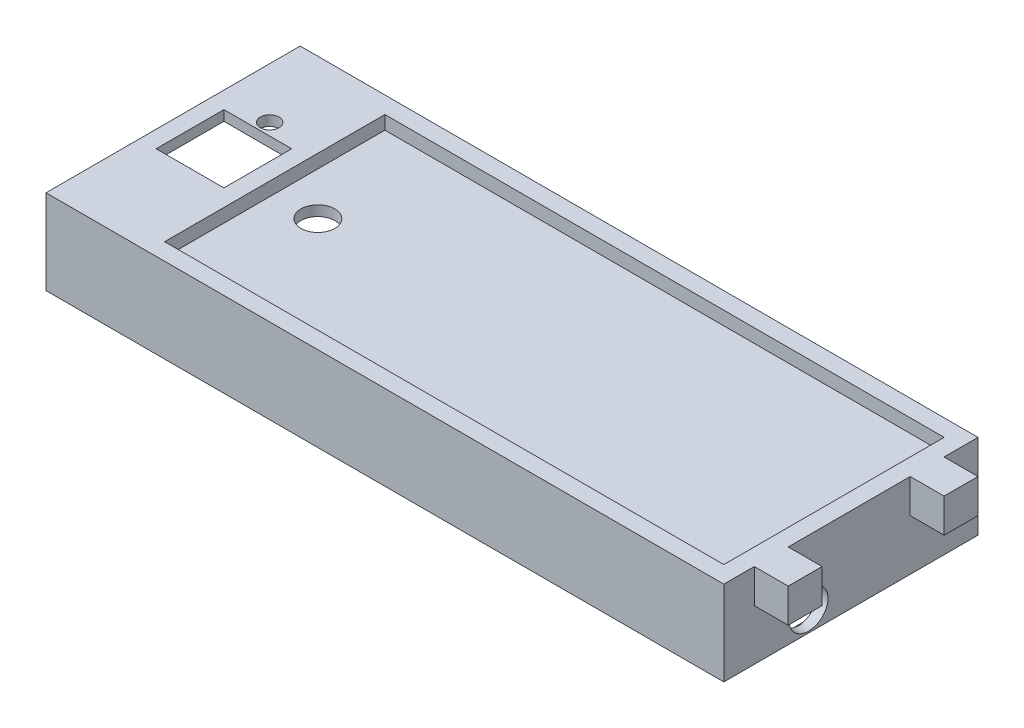
SolidWorks part; units mm, degrees
ref_plane "Front Plane" through (0, 0, 0) normal (0, 0, 1) x (1, 0, 0)
ref_plane "Top Plane" through (0, 0, 0) normal (0, 1, 0) x (1, 0, 0)
ref_plane "Right Plane" through (0, 0, 0) normal (1, 0, 0) x (0, 0, -1)
sketch "Sketch1" plane through (0, 0, 0) normal (0, 1, 0) x (1, 0, 0)
  line L1 (-60, 37.5) -> (140, 37.5)
  line L2 (-60, 37.5) -> (-60, -37.5)
  line L3 (-60, -37.5) -> (140, -37.5)
  line L4 (140, 37.5) -> (140, -37.5)
  point P0 (0, 0)
  dimension "D1" = 200
  dimension "D2" = 75
extrude "Boss-Extrude1" add sketch "Sketch1" along normal blind 25
sketch "Sketch9" plane through (0, 25, 0) normal (0, 1, 0) x (1, 0, 0)
  line L1 (-30, 32.5) -> (135, 32.5)
  line L2 (-30, 32.5) -> (-30, -32.5)
  line L3 (-30, -32.5) -> (135, -32.5)
  line L4 (135, 32.5) -> (135, -32.5)
  line L5 (140, -37.5) -> (140, 37.5) construction
  point P4 (135, 0)
  dimension "D1" = 165
  dimension "D2" = 65
  dimension "D3" = 0
  dimension "D4" = 5
extrude "Cut-Extrude5" cut sketch "Sketch9" against normal blind 4
shell "Shell3" thickness 3 removed face at (40, 0, 0) removed face at (-60, 12.5, 0)
sketch "Sketch14" plane through (140, 0, 0) normal (1, 0, 0) x (0, 0, -1)
  line L0 (37.5, 25) -> (37.5, 0) construction
  line L1 (-28.5, 25) -> (-18.5, 25)
  line L2 (-28.5, 25) -> (-28.5, 15)
  line L3 (-28.5, 15) -> (-18.5, 15)
  line L4 (-18.5, 25) -> (-18.5, 15)
  line L5 (17.5, 25) -> (27.5, 25)
  line L6 (17.5, 25) -> (17.5, 15)
  line L7 (17.5, 15) -> (27.5, 15)
  line L8 (27.5, 25) -> (27.5, 15)
  line L9 (-37.5, 25) -> (37.5, 25) construction
  dimension "D1" = 10
  dimension "D2" = 10
  dimension "D3" = 10
  dimension "D4" = 36
extrude "Boss-Extrude5" add sketch "Sketch14" along normal blind 10
sketch "Sketch15" plane through (0, 21, 0) normal (0, 1, 0) x (1, 0, 0)
  circle A0 centre (-17.2823, 0) radius 5
extrude "Cut-Extrude7" cut sketch "Sketch15" against normal through all
sketch "Sketch16" plane through (0, 25, 0) normal (0, 1, 0) x (1, 0, 0)
  line L0 (-30, 32.5) -> (-30, -32.5) construction
  line L1 (-55, -10) -> (-35, -10)
  line L2 (-55, -10) -> (-55, 10)
  line L3 (-55, 10) -> (-35, 10)
  line L4 (-35, -10) -> (-35, 10)
  line L5 (-55, -10) -> (-35, 10) construction
  line L6 (-55, 10) -> (-35, -10) construction
  line L7 (-60, -37.5) -> (140, -37.5) construction
  line L8 (140, 37.5) -> (-60, 37.5) construction
  point P0 (-45, 0)
  dimension "D1" = 20
  dimension "D2" = 20
  dimension "D3" = 5
  dimension "D4" = 27.5
  dimension "D5" = 27.5
extrude "Cut-Extrude8" cut sketch "Sketch16" against normal through all
ref_plane "Plane1" through (0, 0, 0) normal (0, 0, -1) x (-1, 0, 0)
sketch "Sketch19" plane through (140, 0, 0) normal (1, 0, 0) x (0, 0, -1)
  line L1 (-37.5, 0) -> (37.5, 0) construction
  line L3 (-37.5, 25) -> (-37.5, 0) construction
  ellipse E0 centre (-12.5, 6) end of major axis (-6.75, 6) minor radius 5.5
  dimension "D1" = 6
  dimension "D2" = 25
  dimension "D3" = 11.5
  dimension "D4" = 11
sketch "Sketch20" plane through (0, 0, 0) normal (0, 0, -1) x (-1, 0, 0)
  line L1 (-137, 18) -> (-137, 0) construction
  spline S0 degree 2 poles (-140, 6) (-136.1989, 6.6303) (-133.0758, 4.1829) knots 0 0 0 1 1 1
sweep "Cut-Sweep2" cut profiles "Sketch19" path "Sketch20"
sketch "Sketch21" plane through (0, 25, 0) normal (0, 1, 0) x (1, 0, 0)
  line L0 (-55, 0) -> (-35, 0)
  line L1 (-55, 10) -> (-55, -10) construction
  line L2 (-35, -10) -> (-35, 10) construction
  line L3 (-45, 0) -> (-45, 13.5)
  circle A0 centre (-45, 13.5) radius 2.75
  dimension "D2" = 5.5
  dimension "D1" = 13.5
extrude "Cut-Extrude9" cut sketch "Sketch21" against normal through all contours A0
